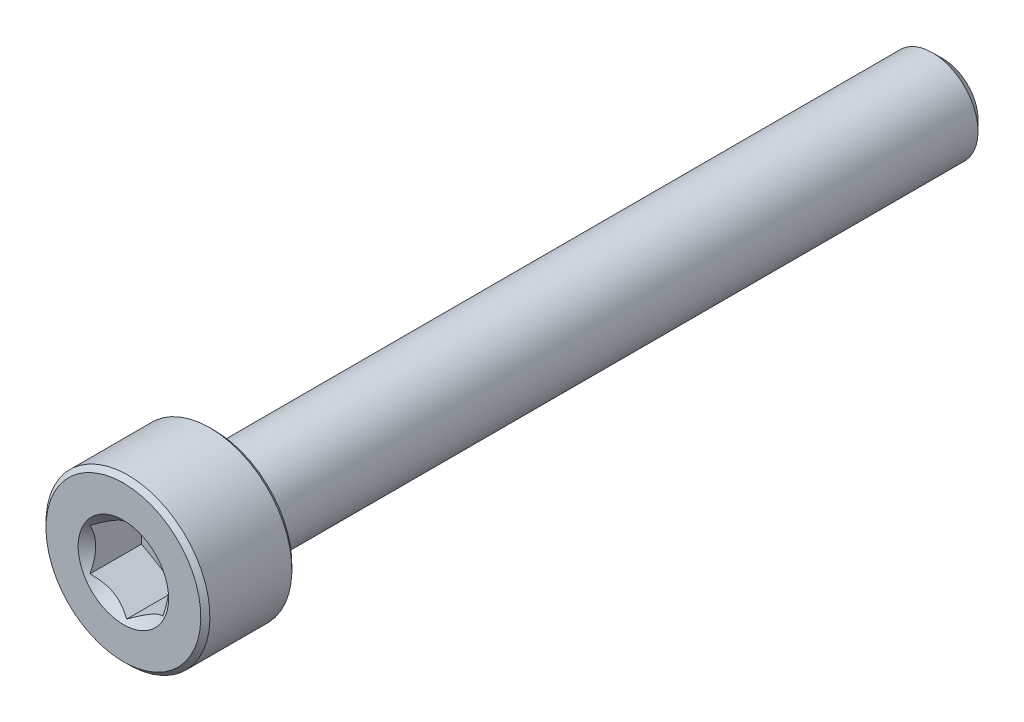
SolidWorks part; units mm, degrees
ref_plane "Front Plane" through (0, 0, 0) normal (0, 0, 1) x (1, 0, 0)
ref_plane "Top Plane" through (0, 0, 0) normal (0, 1, 0) x (1, 0, 0)
ref_plane "Right Plane" through (0, 0, 0) normal (1, 0, 0) x (0, 0, -1)
sketch "Sketch1" plane through (0, 0, 0) normal (1, 0, 0) x (0, 0, -1)
  line L0 (-11.25, 0) -> (11.25, 0) construction
  line L1 (11.25, 0) -> (11.25, 0.9577) construction
  line L2 (11.25, 0.9577) -> (10.9577, 1.25) construction
  line L3 (10.9577, 1.25) -> (10.9125, 1.25) construction
  line L4 (10.9125, 1.25) -> (-8.75, 1.25) construction
  line L5 (-8.75, 1.25) -> (-8.75, 2.25) construction
  line L6 (-8.75, 2.25) -> (-11.25, 2.25) construction
  line L7 (-11.25, 2.25) -> (-11.25, 0) construction
  line L8 (11.25, 0.9577) -> (11.25, 1.25) construction
  line L9 (11.2219, 1.2987) -> (11.4469, 0.909) construction
  line L10 (11.4469, 0.909) -> (11.6719, 1.2987) construction
  line L11 (11.6719, 1.2987) -> (11.2219, 1.2987) construction
  line L12 (11.4469, 1.2987) -> (11.4469, 1.25) construction
  line L13 (11.4469, 0.909) -> (11.4469, 0.9577) construction
  line L14 (11.4188, 0.9577) -> (11.475, 0.9577) construction
  line L15 (11.25, 1.25) -> (11.6438, 1.25) construction
  line L16 (11.2359, 1.2744) -> (11.6578, 1.2744) construction
  line L17 (11.25, 0) -> (11.25, -1.25) construction
  line L18 (-8.875, 2.25) -> (-8.75, 2.125) construction
  line L19 (-11.125, 2.25) -> (-11.25, 2.125) construction
  line L20 (-8.75, 1.25) -> (-8.75, 0) construction
  line L21 (-8.75, 0.625) -> (-2.0833, 0.625) construction
  line L22 (-2.0833, 0.625) -> (4.5833, 0.625) construction
  line L23 (4.5833, 0.625) -> (11.25, 0.625) construction
  line L24 (-2.0833, 0.625) -> (-2.0833, 1.25) construction
  line L25 (-2.0833, 1.25) -> (-2.0833, 2.25) construction
  line L26 (4.5833, 0.625) -> (4.5833, 2.25) construction
  point P0 (-11.25, 1)
  point P3 (10.125, 1.25)
  point P4 (0, 0)
  point P18 (4.5833, 1.25)
  point P22 (11.4469, 0.9577)
  point P24 (10.9125, 1.25)
  point P25 (11.4469, 1.25)
  point P28 (11.4469, 1.2744)
  point P29 (10.125, -1.25)
  point P30 (-2.0833, 1.25)
  point P31 (-10, 2.25)
  point P37 (-9.1875, 2.25)
  point P38 (-11.0625, 2.25)
  point P45 (-2.0833, 0.625)
  point P46 (4.5833, 0.625)
  dimension "D2" = 0.0563
  dimension "D7" = 0.125
  dimension "D8" = 0.125
  dimension "D9" = 0.125
  dimension "D10" = 0.0625
  dimension "D11" = 0.3125
  dimension "Drive Size" = 2
  dimension "Head Diameter" = 4.5
  dimension "Head Height" = 2.5
  dimension "Thread Pitch" = 0.45
  dimension "Thread Dia" = 2.5
  dimension "Length" = 20
  dimension "D12" = 0.3375
  dimension "D4" = 1.125
  dimension "D3" = 45
sketch "Sketch2" plane through (0, 0, 0) normal (1, 0, 0) x (0, 0, -1)
  line L0 (-11.25, 0) -> (-11.25, 2.125)
  line L1 (-11.125, 2.25) -> (-8.875, 2.25)
  line L2 (-8.75, 2.125) -> (-8.75, 1.375)
  line L4 (10.9577, 1.25) -> (11.25, 0.9577)
  line L5 (11.25, 0.9577) -> (11.25, 0)
  line L6 (-8.75, 2.25) -> (-11.25, 2.25) construction
  line L7 (11.25, 0) -> (-11.25, 0)
  line L8 (-11.125, 2.25) -> (-11.25, 2.125) construction
  line L10 (-11.125, 2.25) -> (-11.25, 2.125)
  line L14 (-8.875, 2.25) -> (-8.75, 2.125) construction
  line L16 (-8.875, 2.25) -> (-8.75, 2.125)
  line L17 (-8.75, 1.25) -> (-8.75, 2.25) construction
  line L19 (-8.625, 1.25) -> (10.9577, 1.25)
  line L20 (10.9125, 1.25) -> (-8.75, 1.25) construction
  arc A1 (-8.75, 1.375) -> (-8.625, 1.25) centre (-8.625, 1.375) ccw
  dimension "D3" = 0.125
revolve "Revolve1" add sketch "Sketch2" angle 360 about L7
sketch "Sketch3" plane through (0, 0, 11.25) normal (0, 0, 1) x (1, 0, 0)
  line L1 (1, -0.5774) -> (1, 0.5774)
  line L2 (1, 0.5774) -> (0, 1.1547)
  line L3 (0, 1.1547) -> (-1, 0.5774)
  line L4 (-1, 0.5774) -> (-1, -0.5774)
  line L5 (-1, -0.5774) -> (0, -1.1547)
  line L6 (0, -1.1547) -> (1, -0.5774)
  circle A0 centre (0, 0) radius 1 construction
  circle A1 centre (0, 0) radius 2.25 construction
  circle A2 centre (0, 0) radius 2.25 construction
  circle A3 centre (0, 0) radius 1.1547 construction
  point P13 (0, 0)
  dimension "D1" = 2.3094
extrude "Cut-Extrude1" cut sketch "Sketch3" against normal offset from surface (1.5 mm away) 1 up to face at (0, 2.125, 8.75)
sketch "Sketch4" plane through (0, 0, 11.25) normal (0, 0, 1) x (1, 0, 0)
  circle A0 centre (0, 0) radius 1.2413
  dimension "D1" = 2.4826
extrude "Cut-Extrude2" cut sketch "Sketch4" against normal up to vertex (1.25 mm away) draft 45 up to point (0, 2.25, 10)
sketch "Sketch11" plane through (0, 0, 0) normal (1, 0, 0) x (0, 0, -1)
  line L0 (-11.25, 0) -> (11.25, 0) construction
  line L1 (-11.25, 0) -> (11.25, 0) construction
  line L2 (-5, 0) -> (-5, 1.25) construction
  line L3 (10.9125, 1.25) -> (-8.75, 1.25) construction
  line L4 (7.5, 0) -> (7.5, 1.25) construction
  line L6 (11.25, 0.9577) -> (11.25, 1.25) construction
  point P2 (-5, 0)
  point P3 (7.5, 0)
  dimension "D1" = 3.75
  dimension "D2" = 3.75
sketch "Sketch6" [suppressed] plane through (0, 0, -11.25) normal (0, 0, -1) x (-1, 0, 0)
  circle A0 centre (0, 0) radius 1.25
curve "Helix/Spiral1" [suppressed] pitch 0.45 height 20.45 turns 45.4444
sketch "Sketch10" [suppressed] plane through (0, 0, 0) normal (1, 0, 0) x (0, 0, -1)
  line L0 (-8.625, -2.25) -> (-8.625, 2.25)
  line L5 (-11.25, 0) -> (11.25, 0) construction
  line L6 (-8.625, 1.25) -> (-8.625, -1.25) construction
  point P3 (-8.625, 0)
split "Split1" [suppressed] bodies to split 106
sketch "Sketch7" [suppressed] plane through (0, 0, 0) normal (1, 0, 0) x (0, 0, -1)
  line L0 (11.2359, 1.2744) -> (11.6578, 1.2744)
  line L1 (11.6578, 1.2744) -> (11.475, 0.9577)
  line L2 (11.475, 0.9577) -> (11.4188, 0.9577)
  line L3 (11.4188, 0.9577) -> (11.2359, 1.2744)
sweep "Cut-Sweep1" [suppressed] cut profiles "Sketch7" path "Helix/Spiral1"
sketch "Sketch8" [suppressed] plane through (0, 0, 0) normal (1, 0, 0) x (0, 0, -1)
  line L0 (-8.75, 0) -> (-8.75, 1.25)
  line L1 (-8.625, -1.25) -> (-8.625, 1.25) construction
  line L2 (-8.75, 1.25) -> (-8.625, 1.25)
  line L4 (-8.625, 1.25) -> (-7.9033, 0)
  line L5 (-7.9033, 0) -> (-8.75, 0)
  line L6 (10.9125, 1.25) -> (-8.75, 1.25) construction
  line L7 (-11.25, 0) -> (11.25, 0) construction
  dimension "D1" = 60
revolve "Revolve2" [suppressed] add sketch "Sketch8" angle 360 about L5
equation "\"D2@Sketch1\" = \"Thread Pitch@Sketch1\" / 8"
equation "\"D4@Helix/Spiral1\" = \"Thread Pitch@Sketch1\""
equation "\"D7@Sketch1\" = \"Head Height@Sketch1\" * .05"
equation "\"D8@Sketch1\"=\"D7@Sketch1\""
equation "\"D9@Sketch1\"=\"D7@Sketch1\""
equation "\"D10@Sketch1\"=\"D7@Sketch1\"/2"
equation "\"D11@Sketch1\"=\"D10@Sketch1\"*5"
equation "\"D4@Sketch1\"=\"Thread Pitch@Sketch1\"*2.5"
equation "\"D12@Sketch1\"=\"Thread Pitch@Sketch1\"*.75"
equation "\"D3@Helix/Spiral1\"=\"Length@Sketch1\"+\"Thread Pitch@Sketch1\""
equation "\"D3@Sketch2\"=\"Thread Dia@Sketch1\"*0.05"
equation "\"D1@Sketch11\"=\"Length@Sketch1\"*0.1875"
equation "\"D2@Sketch11\"=\"D1@Sketch11\""
equation "\"D1@Sketch4\"=\"D1@Sketch3\"*1.075"
